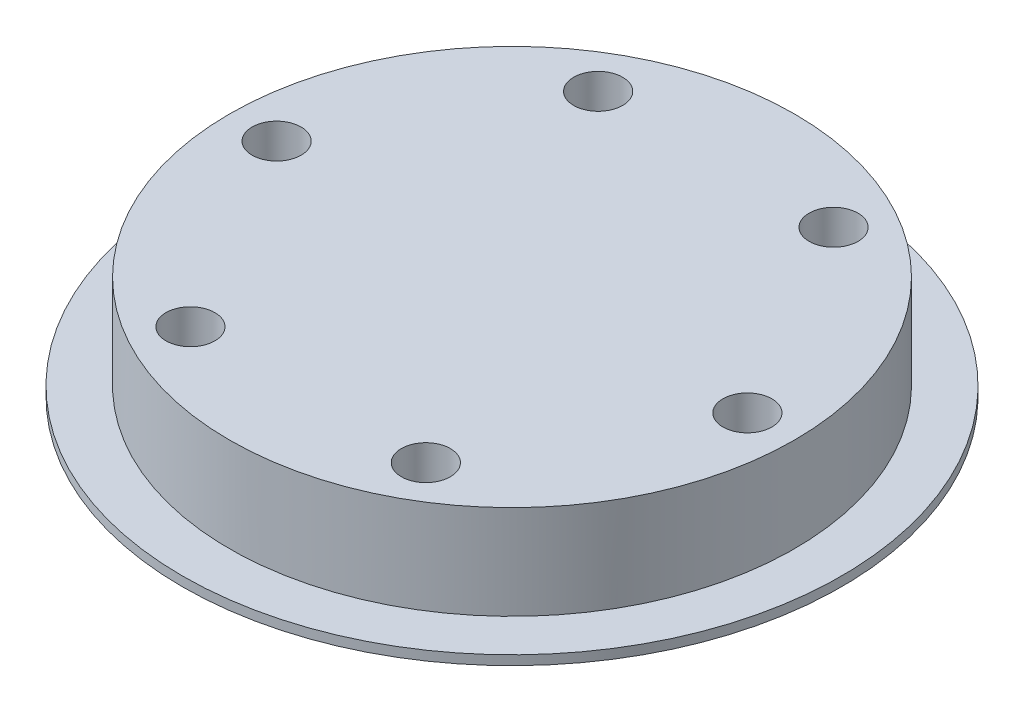
SolidWorks part; units mm, degrees
ref_plane "Front Plane" through (0, 0, 0) normal (0, 0, 1) x (1, 0, 0)
ref_plane "Top Plane" through (0, 0, 0) normal (0, 1, 0) x (1, 0, 0)
ref_plane "Right Plane" through (0, 0, 0) normal (1, 0, 0) x (0, 0, -1)
sketch "Sketch1" plane through (0, 0, 0) normal (0, 1, 0) x (1, 0, 0)
  circle A0 centre (0, 0) radius 30
  point P18 (0, 0)
  dimension "D4" = 60
extrude "Boss-Extrude1" add sketch "Sketch1" along normal blind 11
sketch "Sketch2" plane through (0, 0, 0) normal (0, -1, 0) x (1, 0, 0)
  circle A0 centre (0, 0) radius 35
  dimension "D1" = 70
extrude "Boss-Extrude2" add sketch "Sketch2" against normal blind 1
sketch "Sketch3" plane through (0, 0, 0) normal (0, 1, 0) x (1, 0, 0)
  circle A1 centre (0, 0) radius 25 construction
  circle A2 centre (0, 25) radius 1.5
  circle A3 centre (21.6506, 12.5) radius 1.5
  circle A4 centre (21.6506, -12.5) radius 1.5
  circle A5 centre (0, -25) radius 1.5
  circle A6 centre (-21.6506, -12.5) radius 1.5
  circle A7 centre (-21.6506, 12.5) radius 1.5
  point P30 (0, 0)
  dimension "D1" = 50
  dimension "D2" = 3
  dimension "D3" = 6
extrude "Cut-Extrude1" cut sketch "Sketch3" along normal blind 5
sketch "Sketch4" plane through (0, 0, 0) normal (0, -1, 0) x (1, 0, 0)
  circle A0 centre (0, 0) radius 14
  dimension "D1" = 28
extrude "Cut-Extrude2" cut sketch "Sketch4" against normal blind 7
sketch "Sketch5" plane through (0, 0, 0) normal (0, -1, 0) x (1, 0, 0)
  line L0 (-12.5, 21.6506) -> (0, 0) construction
  line L1 (0, 0) -> (0, 25) construction
  line L2 (0, 25) -> (-21.6506, 12.5) construction
  circle A0 centre (0, 0) radius 25 construction
  circle A1 centre (-12.5, 21.6506) radius 2.6
  circle A2 centre (12.5, 21.6506) radius 2.6
  circle A3 centre (25, 0) radius 2.6
  circle A4 centre (12.5, -21.6506) radius 2.6
  circle A5 centre (-12.5, -21.6506) radius 2.6
  circle A6 centre (-25, 0) radius 2.6
  point P21 (0, 0)
  dimension "D1" = 5.2
  dimension "D2" = 6
extrude "Cut-Extrude3" cut sketch "Sketch5" against normal blind 25
